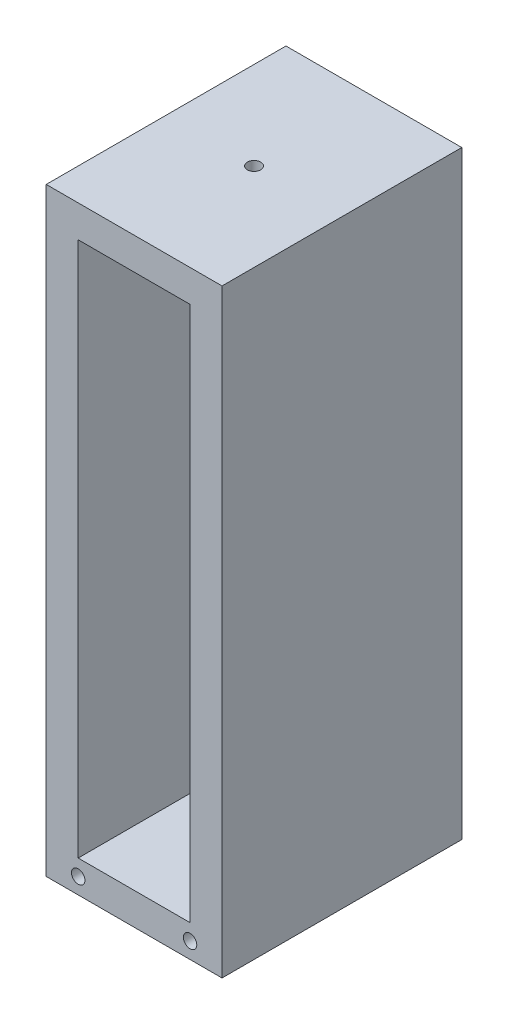
SolidWorks part; units mm, degrees
ref_plane "Front Plane" through (0, 0, 0) normal (0, 0, 1) x (1, 0, 0)
ref_plane "Top Plane" through (0, 0, 0) normal (0, 1, 0) x (1, 0, 0)
ref_plane "Right Plane" through (0, 0, 0) normal (1, 0, 0) x (0, 0, -1)
sketch "Sketch1" plane through (0, 0, 0) normal (0, 0, 1) x (1, 0, 0)
  line L1 (0, 0) -> (55, 0)
  line L2 (0, 0) -> (0, 187.5)
  line L3 (0, 187.5) -> (55, 187.5)
  line L4 (55, 0) -> (55, 187.5)
  line L5 (10, 10) -> (45, 10)
  line L6 (10, 10) -> (10, 177.5)
  line L7 (10, 177.5) -> (45, 177.5)
  line L8 (45, 10) -> (45, 177.5)
  dimension "D1" = 55
  dimension "D2" = 187.5
  dimension "D3" = 10
  dimension "D4" = 10
  dimension "D5" = 10
  dimension "D6" = 10
extrude "Boss-Extrude1" add sketch "Sketch1" against normal blind 75
sketch "Sketch2" plane through (0, 0, 0) normal (0, 0, 1) x (1, 0, 0)
  line L0 (0, 5) -> (55, 5) construction
  line L3 (10, 10) -> (45, 10) construction
  line L4 (27.5, 10) -> (27.5, 0) construction
  line L5 (0, 0) -> (55, 0) construction
  line L8 (0, 187.5) -> (0, 0) construction
  line L9 (55, 0) -> (55, 187.5) construction
  circle A0 centre (10, 5) radius 2
  circle A1 centre (45, 5) radius 2
  dimension "D3" = 4
  dimension "D1" = 5
  dimension "D2" = 17.5
ref_plane "Plane1" through (0, 0, -37.5) normal (0, 0, 1) x (1, 0, 0)
hole_wizard "Tap Drill for M5x0.8 Tap1" positions "Sketch3" profile "Sketch4" hole size "M5x0.8" standard "ANSI Metric"
sketch "Sketch3" plane through (0, 0, 0) normal (0, 0, 1) x (1, 0, 0)
  point P0 (10, 5)
  point P3 (45, 5)
sketch "Sketch4" plane through (10, 5, 0) normal (1, 0, 0) x (0, -1, 0)
  line L0 (0, 0) -> (0, 8.9618)
  line L1 (0, 8.9618) -> (2.1, 7.7)
  line L2 (2.1, 7.7) -> (2.1, 0)
  line L5 (2.1, 0) -> (0, 0)
  line L10 (0, 8.9618) -> (-2.1, 7.7) construction
  line L11 (0, -6.35) -> (0, 107.95) construction
  dimension "Hole Dia." = 4.2
  dimension "Hole Depth" = 7.7
  dimension "Drill Angle" = 118
mirror "Mirror1" about plane through (0, 0, -37.5) normal (0, 0, 1) of "Tap Drill for M5x0.8 Tap1"
hole_wizard "Tap Drill for M5x0.8 Tap2" positions "Sketch8" profile "Sketch9" hole size "M5x0.8" standard "ANSI Metric" end condition through all
sketch "Sketch8" plane through (0, 10, 0) normal (0, 1, 0) x (1, 0, 0)
  line L0 (27.5, 75) -> (27.5, 0) construction
  line L1 (10, 75) -> (45, 75) construction
  line L2 (10, 0) -> (45, 0) construction
  point P0 (27.5, 37.5)
sketch "Sketch9" plane through (27.5, 10, -37.5) normal (1, 0, 0) x (0, 0, 1)
  line L0 (0, 0) -> (0, 10)
  line L1 (0, 10) -> (2.1, 10)
  line L2 (2.1, 10) -> (2.1, 0)
  line L5 (2.1, 0) -> (0, 0)
  line L11 (0, -6.35) -> (0, 107.95) construction
  dimension "Thru Hole Dia." = 4.2
  dimension "Thru Hole Depth" = 10
hole_wizard "Tap Drill for M5x0.8 Tap3" positions "Sketch11" profile "Sketch12" hole size "M5x0.8" standard "ANSI Metric"
sketch "Sketch11" plane through (0, 187.5, 0) normal (0, 1, 0) x (1, 0, 0)
  line L0 (0, 37.5) -> (55, 37.5) construction
  line L1 (0, 75) -> (0, 0) construction
  line L2 (55, 75) -> (55, 0) construction
  point P0 (27.5, 37.5)
sketch "Sketch12" plane through (27.5, 187.5, -37.5) normal (1, 0, 0) x (0, 0, 1)
  line L0 (0, 0) -> (0, 11.2618)
  line L1 (0, 11.2618) -> (2.1, 10)
  line L2 (2.1, 10) -> (2.1, 0)
  line L5 (2.1, 0) -> (0, 0)
  line L10 (0, 11.2618) -> (-2.1, 10) construction
  line L11 (0, -6.35) -> (0, 107.95) construction
  dimension "Hole Dia." = 4.2
  dimension "Hole Depth" = 10
  dimension "Drill Angle" = 118
